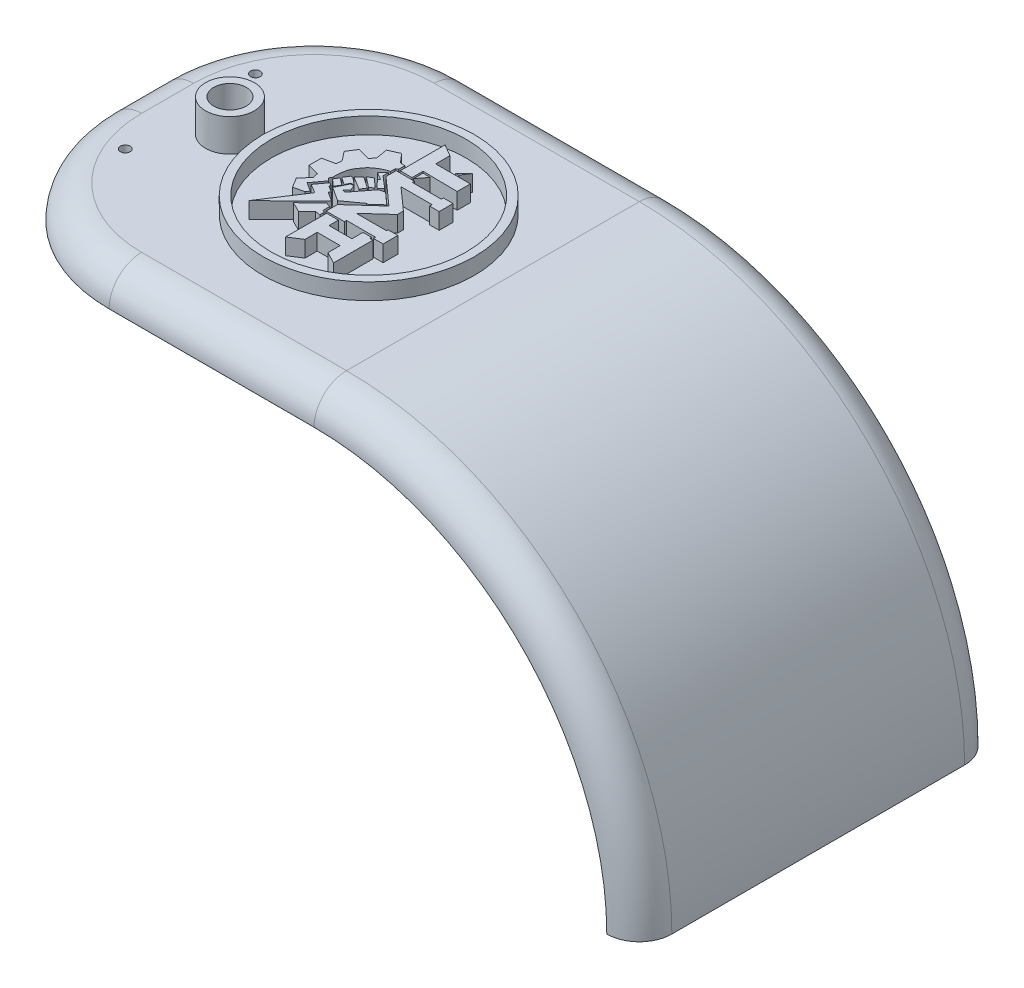
SolidWorks part; units mm, degrees
ref_plane "Alzado" through (0, 0, 0) normal (0, 0, 1) x (1, 0, 0)
ref_plane "Planta" through (0, 0, 0) normal (0, 1, 0) x (1, 0, 0)
ref_plane "Vista lateral" through (0, 0, 0) normal (1, 0, 0) x (0, 0, -1)
sketch "Croquis2" plane through (0, 0, 0) normal (0, 1, 0) x (1, 0, 0)
  line L1 (125, -50) -> (-125, -50)
  line L2 (125, -50) -> (125, 50)
  line L3 (125, 50) -> (-125, 50)
  line L4 (-125, -50) -> (-125, 50)
  line L5 (125, -50) -> (-125, 50) construction
  line L6 (125, 50) -> (-125, -50) construction
  point P0 (0, 0)
  dimension "D1" = 250
  dimension "D2" = 100
extrude "Saliente-Extruir1" add sketch "Croquis2" along normal blind 10
sketch "Croquis5" plane through (0, 10, 0) normal (0, 1, 0) x (1, 0, 0)
  line L0 (-125, -50) -> (125, -50) construction
  line L1 (125, 50) -> (120, 50)
  line L2 (125, 50) -> (125, -50)
  line L3 (125, -50) -> (120, -50)
  line L4 (120, 50) -> (120, -50)
  dimension "D1" = 5
extrude "Saliente-Extruir2" add sketch "Croquis5" along normal blind 10
sketch "Croquis6" plane through (0, 10, 0) normal (0, 1, 0) x (1, 0, 0)
  line L0 (-125, 50) -> (-125, -50) construction
  line L1 (120, 50) -> (-125, 50)
  line L2 (120, 50) -> (120, 40)
  line L3 (120, 40) -> (-125, 40)
  line L4 (-125, 50) -> (-125, 40)
  line L5 (120, 50) -> (120, -50) construction
  line L6 (-125, -50) -> (120, -50)
  line L7 (-125, -50) -> (-125, -40)
  line L8 (-125, -40) -> (120, -40)
  line L9 (120, -50) -> (120, -40)
  dimension "D1" = 10
  dimension "D2" = 10
extrude "Saliente-Extruir3" add sketch "Croquis6" along normal blind 10
sketch "Croquis7" plane through (-125, 0, 0) normal (-1, 0, 0) x (0, 0, 1)
  line L5 (0, 0) -> (0, 32.6209) construction
  line L6 (-50, 0) -> (50, 0) construction
  line L7 (-40, 20) -> (-40, 10) construction
  line L8 (-40, 15) -> (-46.4822, 15)
  line L9 (-40, 15) -> (-40, 10)
  line L10 (-40, 10) -> (-46.4822, 10)
  line L11 (-46.4822, 15) -> (-46.4822, 10)
  line L12 (-50, 20) -> (-40, 20) construction
  line L13 (40, 10) -> (46.4822, 10)
  line L14 (46.4822, 15) -> (46.4822, 10)
  line L15 (40, 15) -> (46.4822, 15)
  line L16 (40, 15) -> (40, 10)
  dimension "D1" = 5
  dimension "D2" = 5
extrude "Cortar-Extruir2" cut sketch "Croquis7" against normal blind 240
sketch "Croquis12" plane through (0, 0, 0) normal (0, -1, 0) x (-1, 0, 0)
  line L1 (109.0854, -9.9901) -> (69.0854, -9.9901)
  line L2 (109.0854, -9.9901) -> (109.0854, 9.8367)
  line L4 (69.0854, -9.9901) -> (69.0854, 9.8367)
  line L7 (69.0854, 9.8367) -> (109.0854, 9.8367)
extrude "Cortar-Extruir5" cut sketch "Croquis12" against normal through all
sketch "Croquis13" plane through (0, 0, 0) normal (0, -1, 0) x (1, 0, 0)
  line L0 (125, -50) -> (-125, -50) construction
  line L1 (125, 50) -> (75, 50)
  line L2 (125, 50) -> (125, -50)
  line L3 (125, -50) -> (75, -50)
  line L4 (75, 50) -> (75, -50)
  dimension "D1" = 50
extrude "Cortar-Extruir6" cut sketch "Croquis13" against normal through all
sketch "Croquis14" plane through (-125, 0, 0) normal (-1, 0, 0) x (0, 0, 1)
  line L1 (-46.4822, 15) -> (46.2751, 15)
  line L2 (-46.4822, 15) -> (-46.4822, 16)
  line L3 (-46.4822, 16) -> (46.2751, 16)
  line L5 (46.4822, 15) -> (46.2751, 15)
  line L6 (46.4822, 15) -> (46.4822, 16)
  line L7 (46.4822, 16) -> (46.2751, 16)
  dimension "D1" = 1
extrude "Cortar-Extruir7" cut sketch "Croquis14" against normal through all
sketch "Croquis15" plane through (0, 10, 0) normal (0, 1, 0) x (1, 0, 0)
  line L0 (75, 46.4822) -> (75, -46.4822) construction
  line L1 (75, 30) -> (-25, 30)
  line L2 (75, 30) -> (75, -30)
  line L3 (75, -30) -> (-25, -30)
  line L4 (-25, 30) -> (-25, -30)
  line L5 (75, 50) -> (-125, 50) construction
  line L6 (-125, -50) -> (75, -50) construction
  dimension "D1" = 20
  dimension "D2" = 20
  dimension "D3" = 100
extrude "Cortar-Extruir8" cut sketch "Croquis15" against normal through all
sketch "Croquis16" plane through (0, 0, 0) normal (0, -1, 0) x (-1, 0, 0)
  circle A0 centre (65.0854, -5.1633) radius 2
  circle A1 centre (65.0854, 4.8367) radius 2
  circle A2 centre (113.0854, 4.8367) radius 2
  circle A3 centre (113.0854, -5.1633) radius 2
extrude "Cortar-Extruir9" cut sketch "Croquis16" against normal through all
sketch "Croquis17" plane through (0, 0, 0) normal (0, -1, 0) x (-1, 0, 0)
  line L0 (125, 0) -> (45.7923, 0) construction
  line L1 (125, 50) -> (125, -50) construction
  line L3 (53, -25) -> (125, -25)
  line L4 (53, -25) -> (53, 25)
  line L5 (53, 25) -> (125, 25)
  line L6 (125, -25) -> (125, 25)
  line L7 (53, -25) -> (125, 25) construction
  line L8 (53, 25) -> (125, -25) construction
  line L9 (58, -20) -> (120, -20)
  line L10 (58, -20) -> (58, 20)
  line L11 (58, 20) -> (120, 20)
  line L12 (120, -20) -> (120, 20)
  line L13 (58, -20) -> (120, 20) construction
  line L14 (58, 20) -> (120, -20) construction
  line L15 (109.0854, 9.8367) -> (69.0854, 9.8367)
  line L16 (109.0854, 9.8367) -> (109.0854, -9.9901)
  line L17 (109.0854, -9.9901) -> (69.0854, -9.9901)
  line L18 (69.0854, 9.8367) -> (69.0854, -9.9901)
  circle A1 centre (113.0854, 4.8367) radius 2
  circle A2 centre (65.0854, 4.8367) radius 2
  circle A3 centre (65.0854, -5.1633) radius 2
  circle A4 centre (113.0854, -5.1633) radius 2
  point P5 (89, 0)
  point P10 (89, 0)
  line M21 (125, -50) -> (125, 50)
  dimension "D1" = 50
  dimension "D2" = 72
  dimension "D3" = 40
  dimension "D4" = 62
extrude "Saliente-Extruir5" add sketch "Croquis17" along normal blind 14 contours L5 L4 L3 L12 L9 L10 L11 M21
fillet "Redondeo1" radius 17 2 edges at (-125, -7, 25) (-125, -7, -25)
fillet "Redondeo2" radius 42 2 edges at (-125, 10, -50) (-125, 10, 50)
sketch "Croquis18" plane through (0, 0, 0) normal (0, -1, 0) x (-1, 0, 0)
  line L0 (-75, 30) -> (25, 30) construction
  line L1 (20.5999, 30) -> (-31.0683, 30)
  line L2 (20.5999, 30) -> (20.5999, 49.0609)
  line L3 (20.5999, 49.0609) -> (-31.0683, 49.0609)
  line L4 (-31.0683, 30) -> (-31.0683, 49.0609)
extrude "Cortar-Extruir10" cut sketch "Croquis18" against normal blind 50
sketch "Croquis19" plane through (0, 0, -50) normal (0, 0, -1) x (-1, 0, 0)
  line L1 (-75, 20) -> (83, 20)
  line L2 (-75, 20) -> (-75, 0)
  line L3 (-75, 0) -> (83, 0)
  line L4 (83, 20) -> (83, 0)
extrude "Saliente-Extruir6" add sketch "Croquis19" along normal blind 5
sketch "Croquis20" plane through (0, 0, 50) normal (0, 0, 1) x (1, 0, 0)
  line L1 (-83, 20) -> (75, 20)
  line L2 (-83, 20) -> (-83, 0)
  line L3 (-83, 0) -> (75, 0)
  line L4 (75, 20) -> (75, 0)
extrude "Saliente-Extruir7" add sketch "Croquis20" along normal blind 5
fillet "Redondeo3" radius 400 2 edges at (-83, 10, -55) (-83, 10, 55)
sketch "Croquis21" plane through (75, 0, 0) normal (1, 0, 0) x (0, 0, -1)
  line L1 (-30, 10) -> (-55, 10)
  line L2 (-30, 10) -> (-30, 0)
  line L3 (-30, 0) -> (-55, 0)
  line L4 (-55, 10) -> (-55, 0)
  line L5 (30, 10) -> (55, 10)
  line L6 (30, 10) -> (30, 0)
  line L7 (30, 0) -> (55, 0)
  line L8 (55, 10) -> (55, 0)
extrude "Saliente-Extruir8" add sketch "Croquis21" along normal blind 10
sketch "Croquis23" plane through (0, 0, -30) normal (0, 0, 1) x (1, 0, 0)
  line L0 (-19.9524, 0) -> (85, 0) construction
  line L1 (85, 10) -> (75, 10)
  line L2 (85, 10) -> (85, 0)
  line L3 (85, 0) -> (75, 0)
  line L4 (75, 10) -> (75, 0)
  dimension "D1" = 10
extrude "Saliente-Extruir10" add sketch "Croquis23" along normal blind 70
sketch "Croquis24" plane through (0, 10, 0) normal (0, 1, 0) x (1, 0, 0)
  line L1 (85, 55) -> (75, 55)
  line L2 (85, 55) -> (85, -55)
  line L3 (85, -55) -> (75, -55)
  line L4 (75, 55) -> (75, -55)
extrude "Saliente-Extruir11" add sketch "Croquis24" along normal blind 150
sketch "Croquis25" plane through (75, 0, 0) normal (-1, 0, 0) x (0, 0, 1)
  line L0 (55, 160) -> (55, 20) construction
  line L1 (-55, 160) -> (55, 160)
  line L2 (-55, 160) -> (-55, 60)
  line L3 (-55, 60) -> (55, 60)
  line L4 (55, 160) -> (55, 60)
  dimension "D1" = 100
extrude "Saliente-Extruir12" add sketch "Croquis25" along normal blind 200
fillet "Redondeo4" radius 100 1 edges at (85, 160, 0)
sketch "Croquis27" plane through (0, 0, 55) normal (0, 0, 1) x (1, 0, 0)
  line L0 (55.7107, 130.7107) -> (-41.9881, 32.9186) construction
  line L1 (-125, 60) -> (75, 60) construction
  line L3 (-125, 160) -> (-14.9326, 160)
  line L4 (-125, 160) -> (-125, 60)
  line L5 (-125, 60) -> (75, 60)
  line L7 (-125, 160) -> (-14.9326, 160)
  line L8 (-125, 160) -> (-125, 149.9326)
  line L9 (-125, 149.9326) -> (-14.9326, 149.9326)
  line L10 (-14.9326, 160) -> (-14.9326, 159.9523)
  line L11 (-125, 149.9326) -> (-14.9326, 149.9326)
  line L12 (-125, 149.9326) -> (-125, 60)
  line L13 (-125, 60) -> (75, 60)
  arc A0 (85, 60) -> (-15, 160) centre (-15, 60) ccw construction
  arc A2 (75, 60) -> (-14.9326, 149.9326) centre (-14.9326, 60) ccw
  arc A3 (55.7107, 130.7107) -> (-14.9326, 159.9523) centre (-14.9326, 60) ccw
  line M6 (-125, 60) -> (75, 60)
extrude "Cortar-Extruir14" cut sketch "Croquis27" against normal blind 200 contours L0 A2 L9 L4 M6 | A2 L0 L13
fillet "Redondeo5" radius 47 2 edges at (-125, 154.9663, -55) (-125, 154.9663, 55)
sketch "Croquis28" plane through (0, 0, 55) normal (0, 0, 1) x (1, 0, 0)
  line L1 (85, 60) -> (-135.6899, 60)
  line L2 (85, 60) -> (85, -20.7852)
  line L3 (85, -20.7852) -> (-135.6899, -20.7852)
  line L4 (-135.6899, 60) -> (-135.6899, -20.7852)
extrude "Cortar-Extruir15" cut sketch "Croquis28" against normal blind 200
sketch "Croquis29" plane through (0, 160, 0) normal (0, 1, 0) x (1, 0, 0)
  line L0 (0, 0) -> (-232.2602, 0) construction
  line L1 (-108.0324, 0) -> (-108.0324, -25.0526) construction
  line L2 (-108.0324, -25.0526) -> (-108.0324, 24.9964) construction
  circle A0 centre (-108.0324, 20) radius 1.5
  circle A1 centre (-108.0324, -20) radius 1.5
  dimension "D1" = 3
  dimension "D2" = 20
extrude "Cortar-Extruir16" cut sketch "Croquis29" against normal blind 30
fillet "Redondeo6" radius 10 7 edges at (55.7107, 130.7107, 55) (55.7107, 130.7107, -55) (-46.5, 160, -55) (-111.234, 160, -41.234) (-125, 160, 0) (-111.234, 160, 41.234) (-46.5, 160, 55)
sketch "Croquis30" plane through (0, 160, 0) normal (0, 1, 0) x (1, 0, 0)
  circle A0 centre (-95.8544, 0) radius 5
  dimension "D1" = 10
extrude "Cortar-Extruir17" cut sketch "Croquis30" against normal blind 30
sketch "Croquis31" plane through (0, 160, 0) normal (0, 1, 0) x (1, 0, 0)
  circle A0 centre (-95.8544, 0) radius 5
  circle A1 centre (-95.8544, 0) radius 7.5
  dimension "D1" = 15
extrude "Saliente-Extruir13" add sketch "Croquis31" along normal blind 10
sketch "Croquis33" plane through (0, 160, 0) normal (0, 1, 0) x (1, 0, 0)
  line L0 (-377.2869, 83.9351) -> (-377.2869, 563.2685) construction
  line L1 (-38.1175, -6.1224) -> (-38.1175, -10.6577)
  line L2 (-38.1175, -10.6577) -> (-41.0697, -10.6577)
  line L3 (-41.0697, -10.6577) -> (-41.0697, -10.0159)
  line L4 (-41.0697, -10.0159) -> (-50.0119, -10.0159)
  line L5 (-50.0119, -10.0159) -> (-50.0119, -10.6577)
  line L6 (-50.0119, -10.6577) -> (-55.6168, -10.6577)
  line L7 (-55.6168, -10.6577) -> (-55.6168, -7.1921)
  line L8 (-55.6168, -7.1921) -> (-47.3164, 0.3382)
  line L9 (-47.3164, 0.3382) -> (-55.6168, 7.7401)
  line L10 (-55.6168, 7.7401) -> (-55.6168, 10.8635)
  line L11 (-55.6168, 10.8635) -> (-50.0119, 10.8635)
  line L12 (-50.0119, 10.8635) -> (-50.0119, 10.2217)
  line L13 (-50.0119, 10.2217) -> (-41.0697, 10.2217)
  line L14 (-41.0697, 10.2217) -> (-41.0697, 10.8635)
  line L15 (-41.0697, 10.8635) -> (-38.1175, 10.8635)
  line L16 (-38.1175, 10.8635) -> (-38.1175, 6.5849)
  line L17 (-38.1175, 6.5849) -> (-41.0697, 6.5849)
  line L18 (-41.0697, 6.5849) -> (-41.0697, 7.3432)
  line L19 (-41.0697, 7.3432) -> (-50.6109, 7.3432)
  line L20 (-50.6109, 7.3432) -> (-43.7643, 1.2377)
  line L21 (-43.7643, 1.2377) -> (-43.7643, -0.6031)
  line L22 (-43.7643, -0.6031) -> (-50.3834, -6.608)
  line L23 (-50.3834, -6.608) -> (-41.0697, -6.608)
  line L24 (-41.0697, -6.608) -> (-41.0697, -6.1224)
  line L25 (-41.0697, -6.1224) -> (-38.1175, -6.1224)
  line L26 (-51.3383, 11.4625) -> (-54.975, 11.4625)
  line L27 (-54.975, 11.4625) -> (-54.975, 25.2694)
  line L28 (-54.975, 25.2694) -> (-51.3383, 23.113)
  line L29 (-51.3383, 23.113) -> (-51.3383, 18.7489)
  line L30 (-51.3383, 18.7489) -> (-40.6932, 18.7489)
  line L31 (-40.6932, 18.7489) -> (-40.6932, 14.6928)
  line L32 (-40.6932, 14.6928) -> (-51.3383, 14.8478)
  line L33 (-51.3383, 14.8478) -> (-51.3383, 11.4625)
  line L34 (-54.975, -11.1672) -> (-51.3383, -11.1672)
  line L35 (-51.3383, -11.1672) -> (-51.3383, -14.0722)
  line L36 (-51.3383, -14.0722) -> (-44.2862, -14.0722)
  line L37 (-44.2862, -14.0722) -> (-44.2862, -10.6577)
  line L38 (-44.2862, -10.6577) -> (-41.6351, -10.6577)
  line L39 (-41.6351, -10.6577) -> (-41.6351, -11.1672)
  line L40 (-41.6351, -11.1672) -> (-40.6932, -11.1672)
  line L41 (-40.6932, -11.1672) -> (-40.6932, -23.323)
  line L42 (-40.6932, -23.323) -> (-44.2862, -21.4334)
  line L43 (-44.2862, -21.4334) -> (-44.2862, -17.6823)
  line L44 (-44.2862, -17.6823) -> (-51.3383, -17.6823)
  line L45 (-51.3383, -17.6823) -> (-51.3383, -21.4334)
  line L46 (-51.3383, -21.4334) -> (-54.975, -23.7743)
  line L47 (-54.975, -23.7743) -> (-54.975, -11.1672)
  line L48 (-62.5946, -2.5545) -> (-61.7719, -3.0344)
  line L49 (-61.7719, -3.0344) -> (-61.7719, -3.6514)
  line L50 (-61.7719, -3.6514) -> (-59.9375, -4.7215)
  line L51 (-59.9375, -4.7215) -> (-60.2881, -5.3225)
  line L52 (-60.2881, -5.3225) -> (-57.4299, -7.1921)
  line L53 (-57.4299, -7.1921) -> (-70.248, -19.7065)
  line L54 (-70.248, -19.7065) -> (-62.2607, -7.4948)
  line L55 (-62.2607, -7.4948) -> (-65.0392, -5.874)
  line L56 (-65.0392, -5.874) -> (-62.5946, -2.5545)
  line L57 (-56.2823, 9.1378) -> (-57.9806, 7.4798)
  line L58 (-57.9806, 7.4798) -> (-55.713, 6.157)
  line L59 (-55.713, 6.157) -> (-56.0781, 5.5311)
  line L60 (-56.0781, 5.5311) -> (-53.8192, 3.2174)
  line L61 (-53.8192, 3.2174) -> (-52.6343, 4.3742)
  line L62 (-52.6343, 4.3742) -> (-56.2823, 7.4798)
  line L63 (-56.2823, 7.4798) -> (-56.2823, 9.1378)
  line L64 (-50.8095, 14.315) -> (-48.6056, 14.315)
  line L65 (-50.8095, 14.315) -> (-50.8095, 11.4625)
  line L66 (-50.8095, 11.4625) -> (-48.6056, 14.315)
  line L67 (-45.808, 19.2986) -> (-44.7916, 19.2986)
  line L68 (-44.7916, 19.2986) -> (-43.1393, 21.8423)
  line L69 (-43.1393, 21.8423) -> (-45.808, 19.2986)
  line L70 (-51.5175, 3.5056) -> (-47.9762, 0.3382)
  line L71 (-47.9762, 0.3382) -> (-50.8775, -2.4273)
  line L72 (-50.8775, -2.4273) -> (-51.5175, -2.4273)
  line L73 (-51.5175, -2.4273) -> (-56.6343, -6.1224)
  line L74 (-56.6343, -6.1224) -> (-60.9135, -3.3429)
  line L75 (-60.9135, -3.3429) -> (-59.0715, 0.3382)
  line L76 (-59.0715, 0.3382) -> (-58.102, 0.3382)
  line L77 (-58.102, 0.3382) -> (-57.4299, -1.3015)
  line L78 (-57.4299, -1.3015) -> (-58.7199, -2.5311)
  line L79 (-58.7199, -2.5311) -> (-57.7659, -2.7692)
  line L80 (-57.7659, -2.7692) -> (-53.2306, 3.1008)
  line L81 (-53.2306, 3.1008) -> (-51.5175, 3.5056)
  line L82 (-54.2644, 3.0074) -> (-55.4075, 2.1819)
  line L83 (-55.4075, 2.1819) -> (-58.5867, 4.6383)
  line L84 (-58.5867, 4.6383) -> (-56.9971, 5.5872)
  line L85 (-56.9971, 5.5872) -> (-54.2644, 3.0074)
  line L86 (-55.4075, 1.7966) -> (-56.4195, 0.2387)
  line L87 (-56.4195, 0.2387) -> (-60.4315, 2.6977)
  line L88 (-60.4315, 2.6977) -> (-58.866, 4.1899)
  line L89 (-58.866, 4.1899) -> (-55.4075, 1.7966)
  line L90 (-58.2429, 0.5836) -> (-59.2268, 0.5836)
  line L91 (-59.2268, 0.5836) -> (-59.9375, -0.8368)
  line L92 (-59.9375, -0.8368) -> (-62.189, 0.7212)
  line L93 (-62.189, 0.7212) -> (-61.1581, 2.4033)
  line L94 (-61.1581, 2.4033) -> (-60.4315, 2.4033)
  line L95 (-60.4315, 2.4033) -> (-58.2429, 0.5836)
  line L96 (-60.1158, -1.3015) -> (-61.1581, -3.002)
  line L97 (-61.1581, -3.002) -> (-63.1838, -1.0895)
  line L98 (-63.1838, -1.0895) -> (-62.3088, 0.3382)
  line L99 (-62.3088, 0.3382) -> (-60.1158, -1.3015)
  line L100 (-56.2823, 9.8083) -> (-56.2823, 11.2382)
  line L101 (-56.2823, 11.2382) -> (-55.6168, 11.6598)
  line L102 (-55.6168, 11.6598) -> (-55.6168, 13.548)
  line L103 (-55.6168, 13.548) -> (-56.9971, 13.548)
  line L104 (-56.9971, 13.548) -> (-59.3477, 16.2977)
  line L105 (-59.3477, 16.2977) -> (-62.5946, 14.8478)
  line L106 (-62.5946, 14.8478) -> (-61.9875, 11.2382)
  line L107 (-61.9875, 11.2382) -> (-63.1838, 9.8083)
  line L108 (-63.1838, 9.8083) -> (-66.9188, 10.8635)
  line L109 (-66.9188, 10.8635) -> (-68.7519, 7.9935)
  line L110 (-68.7519, 7.9935) -> (-66.5179, 5.1447)
  line L111 (-66.5179, 5.1447) -> (-66.7161, 3.5056)
  line L112 (-66.7161, 3.5056) -> (-70.4385, 2.6977)
  line L113 (-70.4385, 2.6977) -> (-70.4385, -1.0895)
  line L114 (-70.4385, -1.0895) -> (-66.9188, -2.0838)
  line L115 (-66.9188, -2.0838) -> (-66.5785, -3.6514)
  line L116 (-66.5785, -3.6514) -> (-68.963, -6.5014)
  line L117 (-68.963, -6.5014) -> (-67.1303, -9.4946)
  line L118 (-67.1303, -9.4946) -> (-64.0669, -8.7004)
  line L119 (-64.0669, -8.7004) -> (-63.3807, -7.7758)
  line L120 (-63.3807, -7.7758) -> (-66.1104, -6.0322)
  line L121 (-66.1104, -6.0322) -> (-63.3092, -2.2576)
  line L123 (-63.3092, -2.2576) -> (-64.0669, -1.4316)
  line L124 (-64.0669, -1.4316) -> (-63.619, -0.6031)
  line L125 (-57.7659, -8.4196) -> (-56.2823, -8.8819)
  line L126 (-56.2823, -8.8819) -> (-56.2823, -11.0403)
  line L127 (-56.2823, -11.0403) -> (-55.6168, -11.2477)
  line L128 (-55.6168, -11.2477) -> (-55.6168, -12.6182)
  line L129 (-55.6168, -12.6182) -> (-57.2239, -12.3575)
  line L130 (-57.2239, -12.3575) -> (-59.7096, -15.0127)
  line L131 (-59.7096, -15.0127) -> (-62.8858, -13.4768)
  line L132 (-62.8858, -13.4768) -> (-57.7659, -8.4196)
  circle A0 centre (-52.411, 0.7212) radius 29.4012
  spline S0 degree 3 poles (-56.2823, 9.8083) (-57.459, 9.4869) (-59.0868, 8.6974) (-60.9839, 7.2082) (-61.9511, 5.7792) (-63.0073, 4.3978) (-63.5335, 2.1791) (-63.6794, 0.5103) (-63.619, -0.6031) knots 0 0 0 0 0.262642 0.388867 0.515773 0.634726 0.760834 1 1 1 1
extrude "Saliente-Extruir14" add sketch "Croquis33" along normal blind 5 contours L47 L34 L35 L36 L37 L38 L39 L40 L41 L42 L43 L44 L45 L46 | L25 L1 L2 L3 L4 L5 L6 L7 L8 L9 L10 L11 L12 L13 L14 L15 L16 L17 L18 L19 L20 L21 L22 L23 L24 | L56 L48 L49 L50 L51 L52 L53 L54 L55 | L132 L125 L126 L127 L128 L129 L130 L131 | L124 S0 L100 L101 L102 L103 L104 L105 L106 L107 L108 L109 L110 L111 L112 L113 L114 L115 L116 L117 L118 L119 L120 L121 L123 | L99 L96 L97 L98 | L95 L90 L91 L92 L93 L94 | L89 L86 L87 L88 | L85 L82 L83 L84 | L63 L57 L58 L59 L60 L61 L62 | L81 L70 L71 L72 L73 L74 L75 L76 L77 L78 L79 L80 | L33 L26 L27 L28 L29 L30 L31 L32 | L66 L64 L65 | L69 L67 L68
sketch "Croquis34" plane through (0, 160, 0) normal (0, 1, 0) x (1, 0, 0)
  circle A0 centre (-53.1906, 0) radius 30
  circle A1 centre (-53.1906, 0) radius 32.5
  dimension "D1" = 60
  dimension "D2" = 65
extrude "Saliente-Extruir15" add sketch "Croquis34" along normal blind 5
